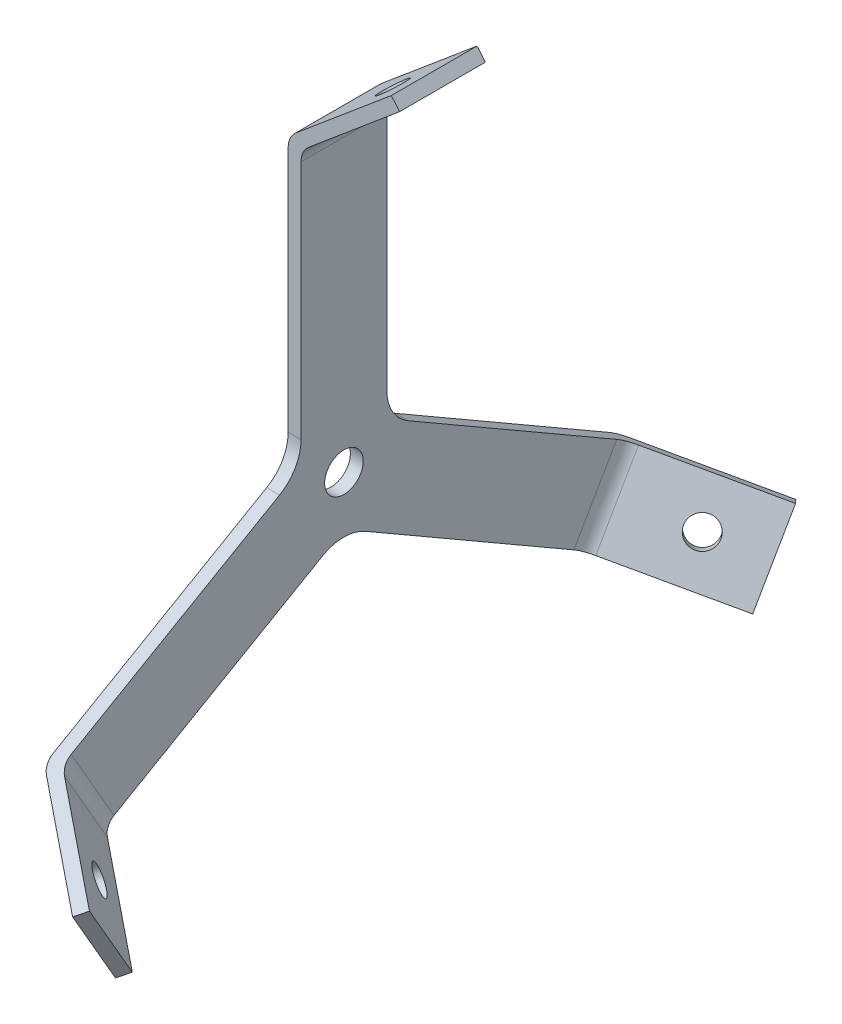
SolidWorks part; units mm, degrees
ref_plane "Спереди" through (0, 0, 0) normal (0, 0, 1) x (1, 0, 0)
ref_plane "Сверху" through (0, 0, 0) normal (0, 1, 0) x (1, 0, 0)
ref_plane "Справа" through (0, 0, 0) normal (1, 0, 0) x (0, 0, -1)
sketch "Эскиз1" plane through (0, 0, 0) normal (0, 0, 1) x (1, 0, 0)
  line L0 (0, 0) -> (0, 69.0674)
  line L1 (1.7861, 72.8976) -> (24.053, 91.5818)
  line L2 (24.053, 91.5818) -> (25.9813, 89.2836)
  line L3 (25.9813, 89.2836) -> (4.7861, 71.4987)
  line L4 (3, 67.6685) -> (3, 0)
  line L5 (3, 0) -> (0, 0)
  line L6 (-16.322, 0) -> (29.4974, 0) construction
  arc A0 (0, 69.0674) -> (1.7861, 72.8976) centre (5, 69.0674) cw
  arc A1 (4.7861, 71.4987) -> (3, 67.6685) centre (8, 67.6685) ccw
  point P13 (3, 70)
  dimension "D6" = 5
  dimension "D1" = 70
  dimension "D2" = 30
  dimension "D3" = 3
  dimension "D4" = 3
  dimension "D5" = 130
extrude "Бобышка-Вытянуть1" add sketch "Эскиз1" along normal blind 10 and the other way blind 10
ref_axis "Ось1" through (-26.5816, 0, 0) along (1, 0, 0)
pattern_circular "Круговой массив1" count 3 over 360 about axis through (-26.5816, 0, 0) along (1, 0, 0) of "Бобышка-Вытянуть1"
fillet "Скругление2" radius 10 3 edges at (1.5, 5.7735, 10) (1.5, -11.547, 0) (1.5, 5.7735, -10)
hole_wizard "Отверстие с зазором M82" positions "Трехмерный эскиз2" profile "Эскиз5" hole size "M8" standard "ISO" end condition through all
sketch3d "Трехмерный эскиз2"
  point P0 (0, 0, 0)
sketch "Эскиз5" plane through (0, 0, 0) normal (0, 1, 0) x (0, 0, 1)
  line L0 (0, 0) -> (0, 25.9813)
  line L1 (0, 25.9813) -> (4.5, 25.9813)
  line L2 (4.5, 25.9813) -> (4.5, 0)
  line L5 (4.5, 0) -> (0, 0)
  line L11 (0, -6.35) -> (0, 107.95) construction
  dimension "Диаметр сквозного отверстия" = 9
  dimension "Глубина сквозного отверстия" = 25.9813
ref_plane "Плоскость1" through (-33.2287, 39.6005, 0) normal (0.6428, -0.766, 0) x (0, 0, -1)
sketch "Эскиз7" plane through (-33.2287, 39.6005, 0) normal (0.6428, -0.766, 0) x (0, 0, -1)
  line L2 (10, 49.6248) -> (-10, 49.6248) construction
  line L3 (-10, 49.6248) -> (-10, 77.2933) construction
  point P0 (0, 64.6248)
  dimension "D1" = 15
  dimension "D2" = 10
hole_wizard "Отверстие с зазором M61" positions "Трехмерный эскиз3" profile "Эскиз8" hole size "M6" standard "ISO" end condition through all
sketch3d "Трехмерный эскиз3"
  point P0 (16.2767, 81.1405, 0)
sketch "Эскиз8" plane through (16.2767, 81.1405, 0) normal (0, 0, 1) x (0.766, 0.6428, 0)
  line L0 (0, 0) -> (0, 25.0951)
  line L1 (0, 25.0951) -> (3.3, 25.0951)
  line L2 (3.3, 25.0951) -> (3.3, 0)
  line L5 (3.3, 0) -> (0, 0)
  line L11 (0, -6.35) -> (0, 107.95) construction
  dimension "Диаметр сквозного отверстия" = 6.6
  dimension "Глубина сквозного отверстия" = 25.0951
ref_axis "Ось2" through (22.6769, 0, 0) along (-1, 0, 0)
pattern_circular "Круговой массив2" count 3 over 360 about axis through (22.6769, 0, 0) along (-1, 0, 0) of "Отверстие с зазором M61"
